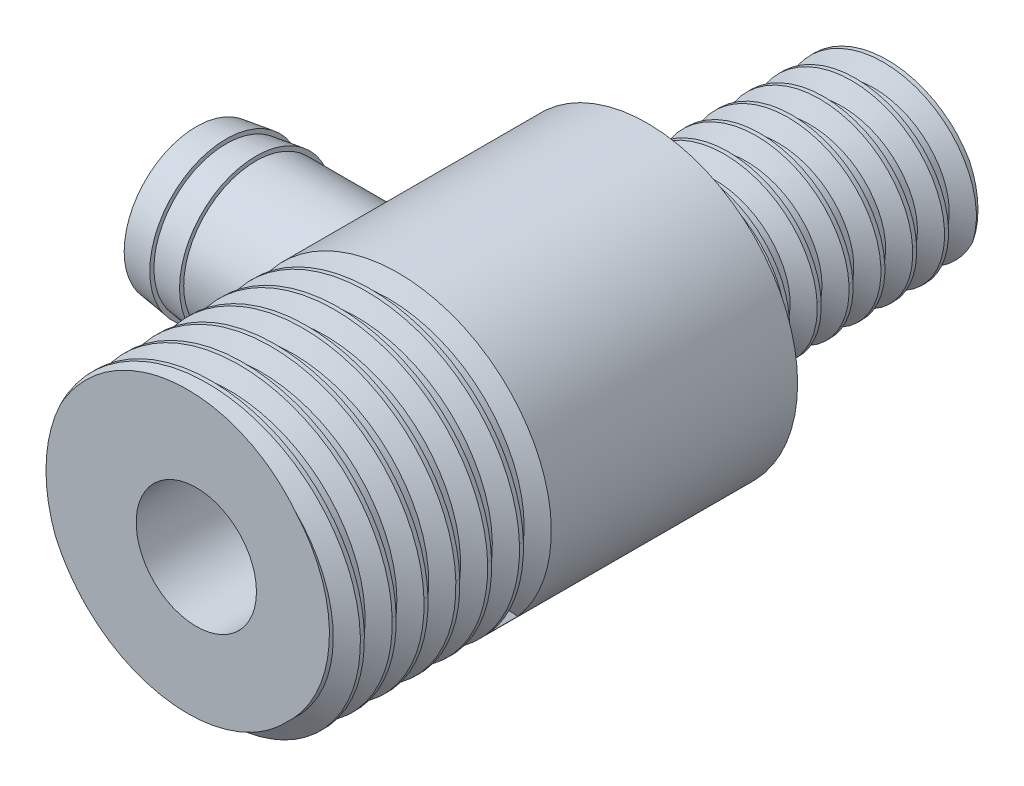
SolidWorks part; units mm, degrees
ref_plane "前视基准面" through (0, 0, 0) normal (0, 0, 1) x (1, 0, 0)
ref_plane "上视基准面" through (0, 0, 0) normal (0, 1, 0) x (1, 0, 0)
ref_plane "右视基准面" through (0, 0, 0) normal (1, 0, 0) x (0, 0, -1)
sketch "草图1" plane through (0, 0, 0) normal (0, 1, 0) x (1, 0, 0)
  line L0 (-14.708, 0) -> (14.708, 0) construction
  line L1 (0, 14.1423) -> (0, -14.1423) construction
  line L2 (0, -8) -> (-5, -8)
  line L3 (-5, -8) -> (-5, 7)
  line L4 (-5, 7) -> (-3, 7)
  line L5 (-3, 7) -> (-3, 15)
  line L6 (-3, 15) -> (0, 15)
  line L7 (-14.3431, 2) -> (14.3431, 2) construction
  line L8 (0, -8) -> (0, 15)
  point P4 (0, 0)
  point P8 (0, 0)
  point P17 (0, 2)
  dimension "D1" = 5
  dimension "D2" = 3
  dimension "D3" = 15
  dimension "D4" = 10
  dimension "D5" = 8
  dimension "D6" = 8
revolve "旋转1" add sketch "草图1" angle 360 about L8
sketch "草图3" plane through (0, 0, 0) normal (0, 1, 0) x (1, 0, 0)
  line L0 (-14.3431, 2) -> (14.3431, 2) construction
  line L1 (-14.3431, 2) -> (14.3431, 2) construction
  line L2 (0, -16.2334) -> (0, 16.2334) construction
  line L3 (0, 4.4) -> (-8.0194, 4.4)
  line L4 (-8.0194, 4.4) -> (-8.0194, 4.5391)
  line L5 (-8.0194, 4.5391) -> (-9.0097, 4.4)
  line L6 (-9.0097, 4.4) -> (-9.0097, 4.5391)
  line L7 (-9.0097, 4.5391) -> (-10, 4.4)
  line L8 (-10, 4.4) -> (-10, 2)
  line L9 (0, 4.4) -> (0, 2)
  line L11 (-10, 2) -> (0, 2)
  point P6 (0, 0)
  dimension "D1" = 2.4
  dimension "D2" = 10
  dimension "D3" = 1
revolve "旋转3" add sketch "草图3" angle 360 about L1
combine bodies "组合1" operation type add bodies to combine 106 109
sketch "草图4" plane through (-10, 0, 0) normal (-1, 0, 0) x (0, 0, 1)
  circle A0 centre (-2, 0) radius 1.5
  dimension "D1" = 3
extrude "切除-拉伸3" cut sketch "草图4" against normal blind 10
sketch "草图2" plane through (0, 0, 8) normal (0, 0, 1) x (1, 0, 0)
  circle A0 centre (0, 0) radius 2
  dimension "D1" = 4
extrude "切除-拉伸2" cut sketch "草图2" against normal blind 12
thread "螺纹线1" pitch 1.0583 method cut profile "螺纹线轮廓1" start angle 0, offset 1, length 7, pitch 1.0583, diameter 10
ref_plane "基准面1" through (-5, 0, 9) normal (0, -1, 0) x (-1, 0, 0)
sketch "螺纹线轮廓1" plane through (-5, 0, 9) normal (0, -1, 0) x (-1, 0, 0)
  line L0 (0, 0) -> (0, 1.0583) construction
  line L11 (0, 0) -> (0, 0.926)
  line L12 (0, 0.926) -> (-0.5728, 0.5953)
  line L13 (-0.5728, 0.5953) -> (-0.5728, 0.3307)
  line L15 (-0.5728, 0.3307) -> (0, 0)
  line L17 (-0.5728, 0.463) -> (0, 0.463) construction
  point P2 (0, 0)
  dimension "Pitch" = 1.0583
  dimension "Profile_Angle" = 60
  dimension "Profile_Land" = 0.2646
  dimension "Profile_Height" = 0.5728
thread "螺纹线2" pitch 1.0583 method cut profile "螺纹线轮廓2" start angle 0, offset 1, length 8, pitch 1.0583, diameter 6
ref_plane "基准面2" through (3, 0, -16) normal (0, -1, 0) x (1, 0, 0)
sketch "螺纹线轮廓2" plane through (3, 0, -16) normal (0, -1, 0) x (1, 0, 0)
  line L0 (0, 0) -> (0, 1.0583) construction
  line L11 (0, 0) -> (0, 0.926)
  line L12 (0, 0.926) -> (-0.5728, 0.5953)
  line L13 (-0.5728, 0.5953) -> (-0.5728, 0.3307)
  line L15 (-0.5728, 0.3307) -> (0, 0)
  line L17 (-0.5728, 0.463) -> (0, 0.463) construction
  point P2 (0, 0)
  dimension "Pitch" = 1.0583
  dimension "Profile_Angle" = 60
  dimension "Profile_Land" = 0.2646
  dimension "Profile_Height" = 0.5728
